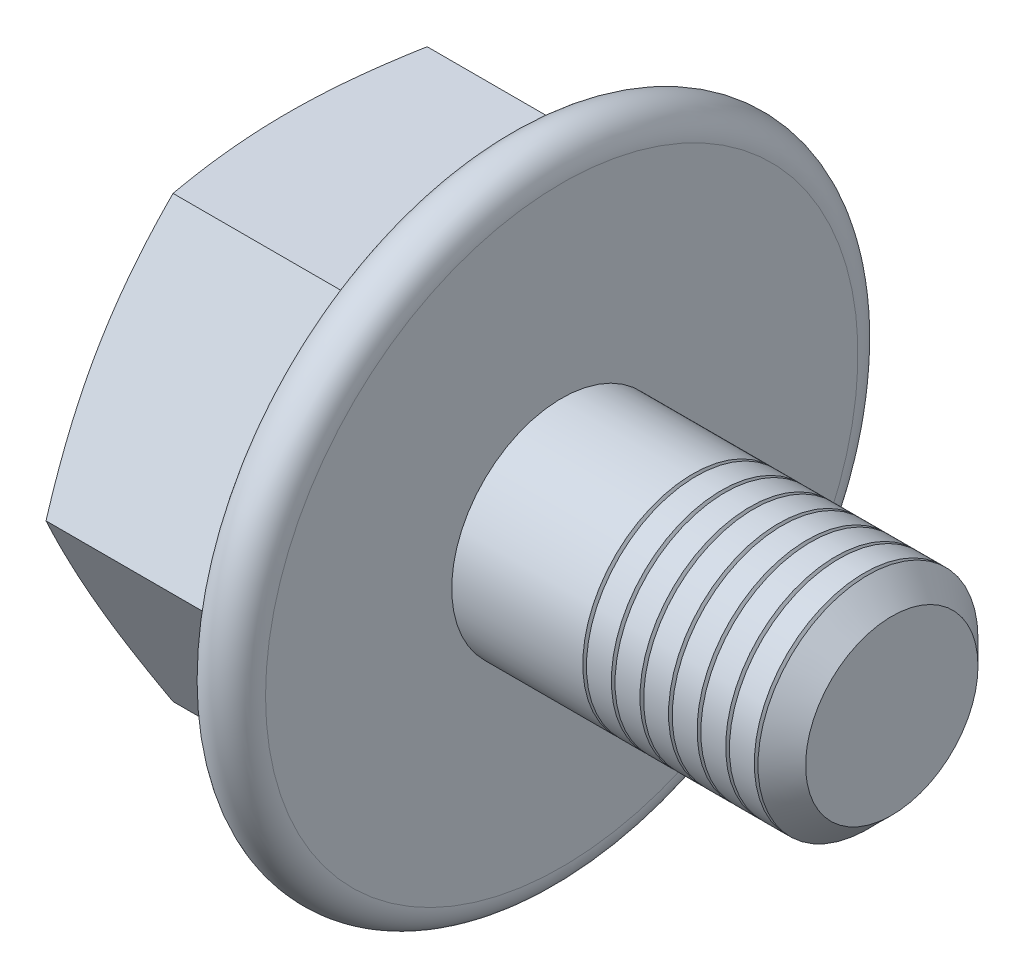
SolidWorks part; units mm, degrees
ref_plane "Front" through (0, 0, 0) normal (0, 0, 1) x (1, 0, 0)
ref_plane "Top" through (0, 0, 0) normal (0, 1, 0) x (1, 0, 0)
ref_plane "Right" through (0, 0, 0) normal (1, 0, 0) x (0, 0, -1)
sketch "Sketch1" plane through (0, 0, 0) normal (1, 0, 0) x (0, 0, -1)
  line L1 (4.6188, 0) -> (2.3094, 4)
  line L2 (2.3094, 4) -> (-2.3094, 4)
  line L3 (-2.3094, 4) -> (-4.6188, 0)
  line L4 (-4.6188, 0) -> (-2.3094, -4)
  line L5 (-2.3094, -4) -> (2.3094, -4)
  line L6 (2.3094, -4) -> (4.6188, 0)
  circle A0 centre (0, 0) radius 4 construction
  dimension "s" = 8
extrude "BaseHead" add sketch "Sketch1" along normal blind 5.4
ref_plane "Plane1" through (7.8, 0, 0) normal (1, 0, 0) x (0, 0, -1)
sketch "Sketch2" plane through (5.4, 0, 0) normal (1, 0, 0) x (0, 0, -1)
  circle A0 centre (0, 0) radius 2
  dimension "d" = 4
extrude "BaseBody" add sketch "Sketch2" along normal blind 6
cosmetic thread "ThreadCosmetic1" [suppressed] parameters "b"=3.6, "D2"=4.134
sketch "Sketch3" plane through (-0.4952, 0, 6.2687) normal (0, 1, 0) x (0, 0, -1)
  line L0 (10.8875, -0.4952) -> (10.8875, -1.139)
  line L2 (10.8875, -1.139) -> (9.1187, -0.4952)
  line L4 (9.1187, -0.4952) -> (10.8875, -0.4952)
  line L5 (6.2687, 4.1693) -> (6.2687, -11.9236) construction
  dimension "D1" = 20
  dimension "da" = 5.7
revolve "HeadChamfer" cut sketch "Sketch3" angle 360 about L5
sketch "Sketch5" plane through (-0.1752, 0, 7.2752) normal (0, 1, 0) x (0, 0, -1)
  line L0 (7.2752, -5.5752) -> (7.2752, -7.1738) construction
  line L2 (7.2752, -5.5752) -> (12.6596, -5.5752)
  line L3 (12.8359, -4.5752) -> (7.2752, -2.5512)
  line L4 (7.2752, -2.5512) -> (7.2752, -5.5752)
  line L7 (7.2752, 4.4893) -> (7.2752, -11.6035) construction
  arc A0 (12.6596, -5.5752) -> (12.8359, -4.5752) centre (12.6596, -5.0596) ccw
  dimension "D3" = 20
  dimension "c" = 1
  dimension "dc" = 11.8
revolve "Flange" add sketch "Sketch5" angle 360 about L0
fillet "HeadFillet" [suppressed] radius 0.25
fillet "FlangeHexFillet" radius 0.3 6 edges
chamfer "Chamfer1" distance 0.433 angle 45 1 edges at (11.4, 0, -2)
sketch "Sketch6" plane through (0, 0, 0) normal (0, 0, 1) x (1, 0, 0)
  line L0 (10.9, 2.067) -> (10.967, 2.067)
  line L1 (10.967, 2.067) -> (10.967, 2)
  line L2 (10.967, 2) -> (10.9335, 1.942)
  line L3 (10.9335, 1.942) -> (10.9, 2)
  line L4 (10.9, 2) -> (10.9, 2.067)
  line L5 (10.967, 2) -> (5.4, 2) construction
  dimension "D1" = 0.067
revolve "Cut-Revolve10" cut sketch "Sketch6" angle 360 about axis through (11.4, 0, 0) along (-1, 0, 0)
pattern_linear "LPattern10" count 7 spacing 0.5196 along (-1, 0, 0) of "Cut-Revolve10"
equation "\"D1@Chamfer1\" = (  \"d@Sketch2\" - \"D2@ThreadCosmetic1\" )  / 2"
equation "\"b@ThreadCosmetic1\" = \"l@BaseBody\" - \"lg@Plane1\""
equation "\"da@Sketch3\" = \"s@Sketch1\""
equation "\"D1@Sketch6\" =  ( \"d@Sketch2\" - \"D2@ThreadCosmetic1\" )  / 2"
equation "\"pitch@LPattern10\" = 1.2 * \"D1@Sketch6\""
equation "\"D1@LPattern10\" = \"b@ThreadCosmetic1\" / \"pitch@LPattern10\""
